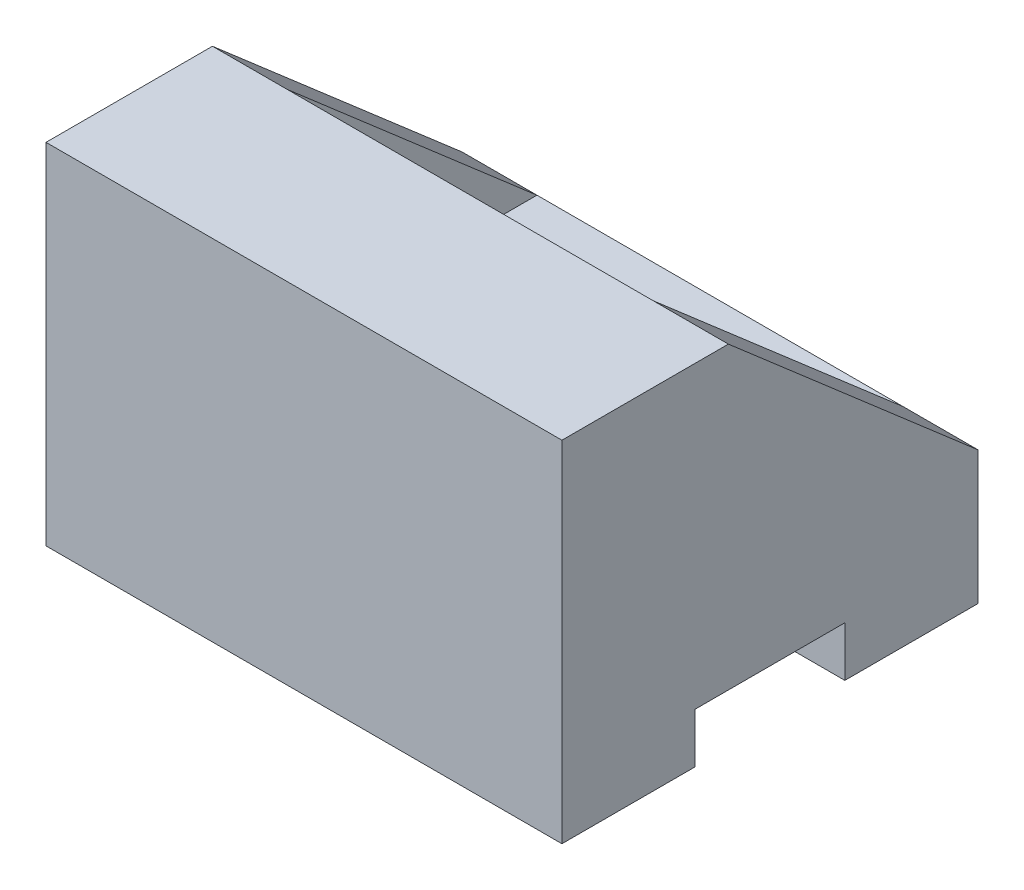
SolidWorks part; units mm, degrees
ref_plane "Front Plane" through (0, 0, 0) normal (0, 0, 1) x (1, 0, 0)
ref_plane "Top Plane" through (0, 0, 0) normal (0, 1, 0) x (1, 0, 0)
ref_plane "Right Plane" through (0, 0, 0) normal (1, 0, 0) x (0, 0, -1)
sketch "Sketch1" plane through (0, 0, 0) normal (1, 0, 0) x (0, 0, -1)
  line L0 (-33.2031, 20.0606) -> (-13.2031, 20.0606)
  line L1 (-13.2031, 20.0606) -> (-13.2031, -5.9394)
  line L2 (-13.2031, -5.9394) -> (16.7969, -5.9394)
  line L3 (16.7969, -5.9394) -> (16.7969, -21.9394)
  line L4 (16.7969, -21.9394) -> (0.7969, -21.9394)
  line L5 (0.7969, -21.9394) -> (0.7969, -15.9394)
  line L6 (0.7969, -15.9394) -> (-17.2031, -15.9394)
  line L7 (-17.2031, -15.9394) -> (-17.2031, -21.9394)
  line L8 (-17.2031, -21.9394) -> (-33.2031, -21.9394)
  line L9 (-33.2031, -21.9394) -> (-33.2031, 20.0606)
  line L10 (-13.2031, 20.0606) -> (16.7969, -5.9394)
  dimension "D1" = 20
  dimension "D2" = 42
  dimension "D3" = 6
  dimension "D4" = 6
  dimension "D5" = 16
  dimension "D6" = 16
  dimension "D7" = 16
  dimension "D8" = 30
extrude "Boss-Extrude1" add sketch "Sketch1" along normal mid plane 62 contours L9 L8 L7 L6 L5 L4 L3 L2 L1 L0 region at (0, -4.4839, 14.6388)
extrude "Boss-Extrude2" add sketch "Sketch1<4>" along normal blind 9 from offset 22 contours L10 L1 L2 region at (0, 2.7273, 3.2031)
sketch "Sketch1<4>" plane through (0, 0, 0) normal (1, 0, 0) x (0, 0, -1) same geometry as "Sketch1"
extrude "Boss-Extrude4" add sketch "Sketch1<14>" against normal blind 9 from offset 22 contours L10 L1 L2 region at (0, 2.7273, 3.2031) offset against normal yes
sketch "Sketch1<14>" plane through (0, 0, 0) normal (1, 0, 0) x (0, 0, -1) same geometry as "Sketch1"
